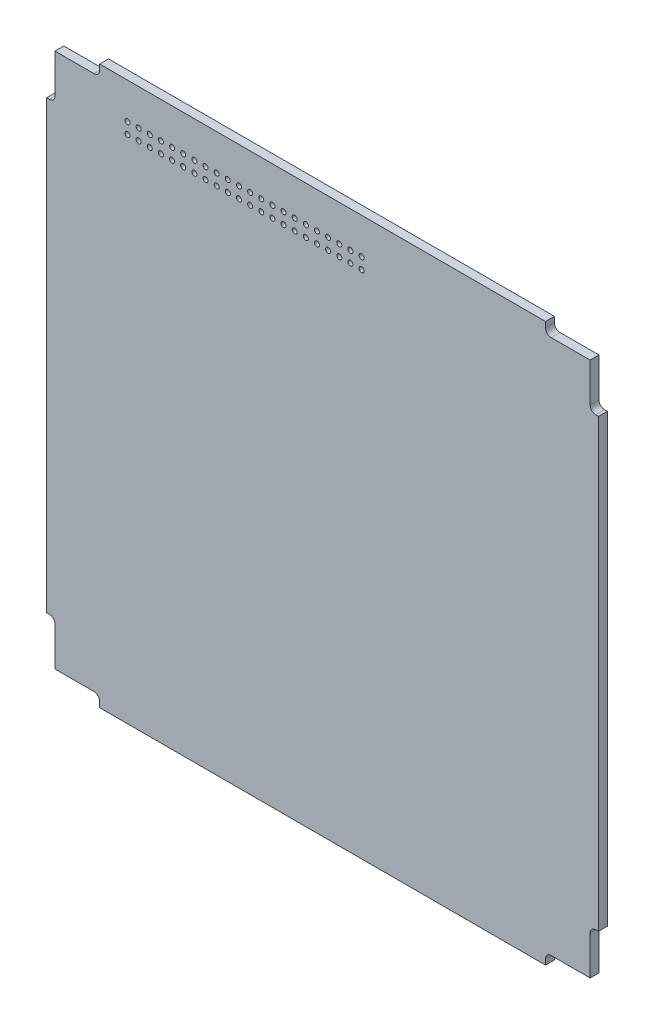
SolidWorks part; units mm, degrees
material "ABS"
ref_plane "Front Plane" through (0, 0, 0) normal (0, 0, 1) x (1, 0, 0)
ref_plane "Top Plane" through (0, 0, 0) normal (0, 1, 0) x (1, 0, 0)
ref_plane "Right Plane" through (0, 0, 0) normal (1, 0, 0) x (0, 0, -1)
sketch "Sketch1" plane through (0, 0, 0) normal (0, 0, 1) x (1, 0, 0)
  line L0 (-40, 50) -> (-40, 48)
  line L1 (-50, -50) -> (50, -50)
  line L2 (-50, -50) -> (-50, 50)
  line L3 (-50, 50) -> (50, 50)
  line L4 (50, -50) -> (50, 50)
  line L5 (-50, -50) -> (50, 50) construction
  line L6 (-50, 50) -> (50, -50) construction
  line L7 (-50, 50) -> (-40, 50)
  line L8 (-50, 50) -> (-50, 40)
  line L9 (-40, 48) -> (-48, 48)
  line L10 (-48, 48) -> (-48, 40)
  line L11 (50, 50) -> (40, 50)
  line L12 (50, 50) -> (50, 40)
  line L13 (-48, 40) -> (-50, 40)
  line L14 (50, 40) -> (48, 40)
  line L15 (-50, -50) -> (-37.8649, -50)
  line L16 (-50, -50) -> (-50, -37.8649)
  line L17 (50, 50) -> (50, 40)
  line L18 (50, 50) -> (40, 50)
  line L19 (50, -50) -> (41.5, -50)
  line L20 (50, -50) -> (50, -41.5)
  line L21 (48, 40) -> (48, 48)
  line L22 (48, 48) -> (40, 48)
  line L23 (40, 48) -> (40, 50)
  line L24 (40, -50) -> (40, -48)
  line L25 (50, -50) -> (40, -50)
  line L26 (50, -50) -> (50, -40)
  line L27 (40, -48) -> (48, -48)
  line L28 (48, -48) -> (48, -40)
  line L29 (48, -40) -> (50, -40)
  line L30 (-50, -40) -> (-48, -40)
  line L31 (-50, -50) -> (-50, -40)
  line L32 (-50, -50) -> (-40, -50)
  line L33 (-48, -40) -> (-48, -48)
  line L34 (-48, -48) -> (-40, -48)
  line L35 (-40, -48) -> (-40, -50)
  point P0 (0, 0)
  point P38 (0, 0)
  dimension "D1" = 100
  dimension "D2" = 100
  dimension "D3" = 2
  dimension "D4" = 10
  dimension "D5" = 4
extrude "Boss-Extrude1" add sketch "Sketch1" along normal blind 1.5875 contours L1 L4 L3 L2 region at (0, 0, 0)
fillet "Fillet1" radius 1 8 edges at (-48, -40, 0.7937) (-40, -48, 0.7937) (40, -48, 0.7937) (48, -40, 0.7937) (48, 40, 0.7937) (40, 48, 0.7937) (-40, 48, 0.7937) (-48, 40, 0.7937)
sketch "Sketch2" plane through (0, 0, 1.5875) normal (0, 0, 1) x (1, 0, 0)
  line L0 (0, 50) -> (0, -50) construction
  line L1 (-40, 50) -> (40, 50) construction
  line L2 (-40, -50) -> (40, -50) construction
  line L4 (-36, 45.8) -> (8, 45.8) construction
  line L5 (-36, 45.8) -> (-36, 43.55) construction
  line L6 (-36, 43.55) -> (8, 43.55) construction
  line L7 (8, 45.8) -> (8, 43.55) construction
  line L8 (-36, 50) -> (8, 50) construction
  line L9 (-36, 50) -> (-36, 45.8) construction
  line L10 (-36, 45.8) -> (8, 45.8) construction
  line L11 (8, 50) -> (8, 45.8) construction
  circle A0 centre (-35, 43.55) radius 0.45
  circle A1 centre (-33, 43.55) radius 0.45
  circle A2 centre (-31, 43.55) radius 0.45
  circle A3 centre (-29, 43.55) radius 0.45
  circle A4 centre (-27, 43.55) radius 0.45
  circle A5 centre (-25, 43.55) radius 0.45
  circle A6 centre (-23, 43.55) radius 0.45
  circle A7 centre (-21, 43.55) radius 0.45
  circle A8 centre (-19, 43.55) radius 0.45
  circle A9 centre (-17, 43.55) radius 0.45
  circle A10 centre (-15, 43.55) radius 0.45
  circle A11 centre (-13, 43.55) radius 0.45
  circle A12 centre (-11, 43.55) radius 0.45
  circle A13 centre (-9, 43.55) radius 0.45
  circle A14 centre (-7, 43.55) radius 0.45
  circle A15 centre (-5, 43.55) radius 0.45
  circle A16 centre (-3, 43.55) radius 0.45
  circle A17 centre (-1, 43.55) radius 0.45
  circle A18 centre (1, 43.55) radius 0.45
  circle A19 centre (3, 43.55) radius 0.45
  circle A20 centre (5, 43.55) radius 0.45
  circle A21 centre (7, 43.55) radius 0.45
  circle A22 centre (-33, 41.55) radius 0.45
  circle A23 centre (-31, 41.55) radius 0.45
  circle A24 centre (-29, 41.55) radius 0.45
  circle A25 centre (-27, 41.55) radius 0.45
  circle A26 centre (-25, 41.55) radius 0.45
  circle A27 centre (-23, 41.55) radius 0.45
  circle A28 centre (-21, 41.55) radius 0.45
  circle A29 centre (-19, 41.55) radius 0.45
  circle A30 centre (-17, 41.55) radius 0.45
  circle A31 centre (-15, 41.55) radius 0.45
  circle A32 centre (-13, 41.55) radius 0.45
  circle A33 centre (-11, 41.55) radius 0.45
  circle A34 centre (-9, 41.55) radius 0.45
  circle A35 centre (-7, 41.55) radius 0.45
  circle A36 centre (-5, 41.55) radius 0.45
  circle A37 centre (-3, 41.55) radius 0.45
  circle A38 centre (-1, 41.55) radius 0.45
  circle A39 centre (1, 41.55) radius 0.45
  circle A40 centre (3, 41.55) radius 0.45
  circle A41 centre (5, 41.55) radius 0.45
  circle A42 centre (7, 41.55) radius 0.45
  circle A43 centre (-35, 41.55) radius 0.45
  dimension "D1" = 0.9
  dimension "D6" = 15
  dimension "D4" = 42
  dimension "D5" = 2
  dimension "D7" = 2.25
  dimension "D8" = 44
  dimension "D10" = 1
  dimension "D11" = 4.2
  dimension "D2" = 22
  dimension "D3" = 2
extrude "Cut-Extrude1" cut sketch "Sketch2" against normal through all
sketch "Sketch5" plane through (0, 0, 0) normal (0, 0, -1) x (-1, 0, 0)
  line L0 (40, -50) -> (-40, -50) construction
  line L1 (-49.5, 50) -> (49.5, 50)
  line L2 (-49.5, 50) -> (-49.5, -50)
  line L3 (-49.5, -50) -> (49.5, -50)
  line L4 (49.5, 50) -> (49.5, -50)
  line L5 (40, 50) -> (-40, 50) construction
  line L6 (50, -40) -> (50, 40) construction
  dimension "D1" = 99
  dimension "D2" = 0.5
extrude "Cut-Extrude3" cut sketch "Sketch5" against normal through all flip side to cut
